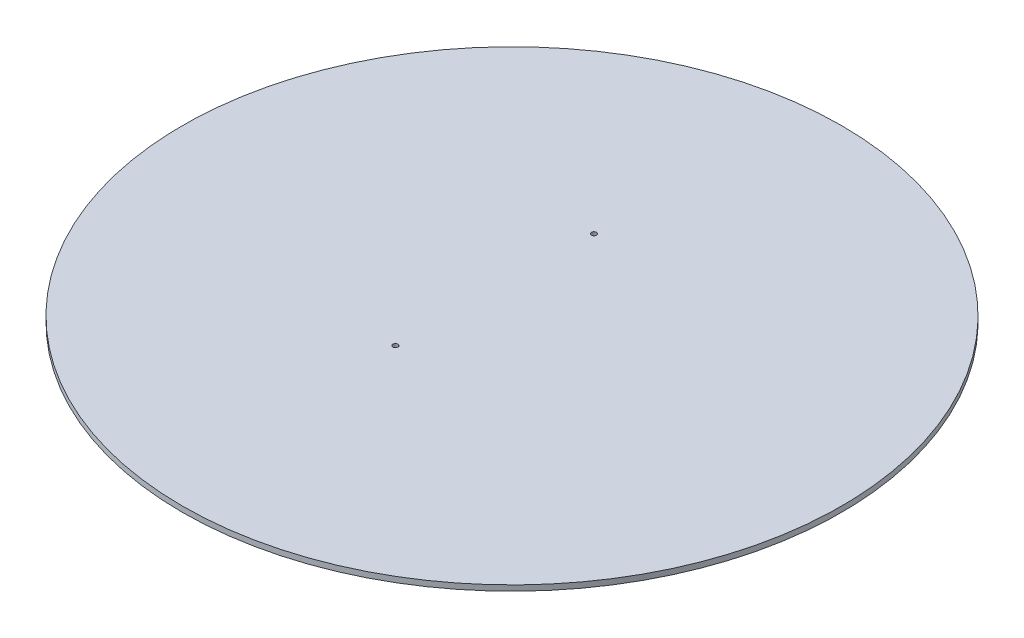
SolidWorks part; units mm, degrees
material "AISI 1020"
ref_plane "Front Plane" through (0, 0, 0) normal (0, 0, 1) x (1, 0, 0)
ref_plane "Top Plane" through (0, 0, 0) normal (0, 1, 0) x (1, 0, 0)
ref_plane "Right Plane" through (0, 0, 0) normal (1, 0, 0) x (0, 0, -1)
sketch "Sketch2" plane through (0, 0, 0) normal (0, 1, 0) x (1, 0, 0)
  circle A0 centre (0, 0) radius 304.8
  dimension "D1" = 609.6
extrude "Boss-Extrude1" add sketch "Sketch2" along normal blind 5.08
extrude "Cut-Extrude1" cut sketch "Sketch3" against normal through all
sketch "Sketch3" plane through (-66.1997, 84.0228, -93.0458) normal (0.1079, 0.9936, 0.0319) x (0.9942, -0.108, -0.0006)
  circle A0 centre (44.3535, -173.1756) radius 2.3495
  circle A1 centre (46.6818, 8.1643) radius 2.3495
